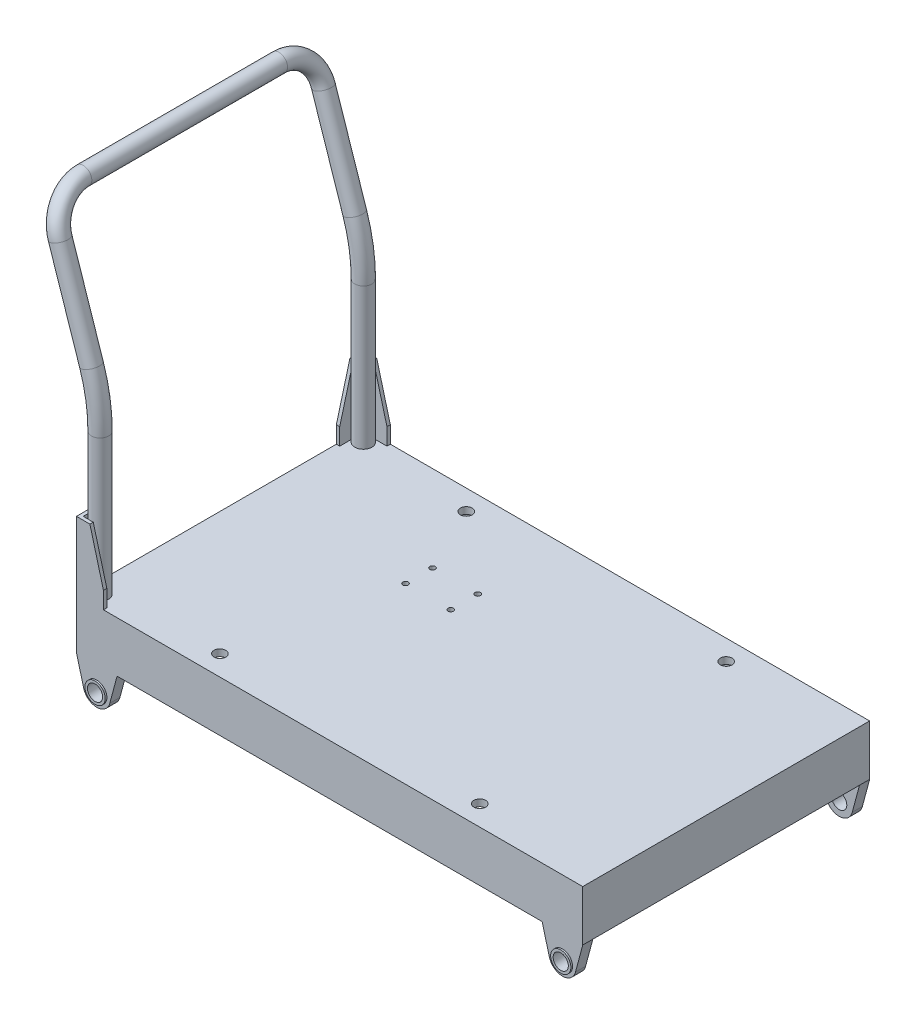
SolidWorks part; units mm, degrees
note: The reader was unsure of these and kept them because the rebuilt part matched: shared geometry of "草圖1<2>".
ref_plane "前基準面" through (0, 0, 0) normal (0, 0, 1) x (1, 0, 0)
ref_plane "上基準面" through (0, 0, 0) normal (0, 1, 0) x (1, 0, 0)
ref_plane "右基準面" through (0, 0, 0) normal (1, 0, 0) x (0, 0, -1)
sketch "草圖1" plane through (0, 0, 0) normal (0, 1, 0) x (1, 0, 0)
  line L1 (-75, -42.5) -> (75, -42.5)
  line L2 (-75, -42.5) -> (-75, 42.5)
  line L3 (-75, 42.5) -> (75, 42.5)
  line L4 (75, -42.5) -> (75, 42.5)
  line L5 (-75, -42.5) -> (75, 42.5) construction
  line L6 (-75, 42.5) -> (75, -42.5) construction
  point P0 (0, 0)
  dimension "D1" = 85
  dimension "D2" = 150
extrude "填料-伸長1" add sketch "草圖1" against normal blind 2
extrude "伸長-薄件1" add sketch "草圖1<2>" against normal blind 15 thin thin type one direction reverse wall 3
sketch "草圖1<2>" plane through (0, 0, 0) normal (0, 1, 0) x (1, 0, 0) same geometry as "草圖1"
sketch "草圖3" plane through (0, 0, 42.5) normal (0, 0, 1) x (1, 0, 0)
  line L0 (-75, 0) -> (75, 0) construction
  line L1 (-5, -12.5) -> (5, -12.5)
  line L2 (-5, -12.5) -> (-5, -2.5)
  line L3 (-5, -2.5) -> (5, -2.5)
  line L4 (5, -12.5) -> (5, -2.5)
  line L5 (-5, -12.5) -> (5, -2.5) construction
  line L6 (-5, -2.5) -> (5, -12.5) construction
  point P0 (0, -7.5)
  dimension "D1" = 10
  dimension "D2" = 7.5
sketch "草圖4" plane through (0, 0, 42.5) normal (0, 0, 1) x (1, 0, 0)
  line L2 (-75, -15) -> (-72.847, -23.0353)
  line L4 (0, 0) -> (0, 11.7436) construction
  line L5 (62.9665, -15) -> (75, -15)
  line L6 (65.1195, -23.0353) -> (62.9665, -15)
  line L7 (75, -15) -> (72.847, -23.0353)
  line L8 (-65.1195, -23.0353) -> (-62.9665, -15)
  line L9 (-62.9665, -15) -> (-75, -15)
  arc A1 (72.847, -23.0353) -> (65.1195, -23.0353) centre (68.9833, -22) cw
  circle A3 centre (68.9833, -22) radius 2.25
  circle A4 centre (-68.9833, -22) radius 2.25
  arc A5 (-72.847, -23.0353) -> (-65.1195, -23.0353) centre (-68.9833, -22) ccw
extrude "填料-伸長2" add sketch "草圖4" against normal blind 3
mirror "鏡射1" about plane through (0, 0, 0) normal (0, 0, 1) of "填料-伸長2"
sketch "草圖6" plane through (0, 0, 0) normal (0, 1, 0) x (1, 0, 0)
  line L0 (-69.8038, 0) -> (0, 0) construction
  line L1 (0, 0) -> (0, -59.3094) construction
  circle A0 centre (-38.5, -36.5) radius 1.75
  circle A1 centre (38.5, -36.5) radius 1.75
  circle A2 centre (38.5, 36.5) radius 1.75
  circle A3 centre (-38.5, 36.5) radius 1.75
  dimension "D1" = 73
  dimension "D2" = 77
  dimension "D3" = 3.5
extrude "除料-伸長2" cut sketch "草圖6" against normal up to next
sketch "草圖7" plane through (0, 0, 0) normal (0, 1, 0) x (1, 0, 0)
  line L0 (0, 0) -> (-65, 0) construction
  line L1 (-65, 0) -> (-65, -35) construction
  line L2 (-69, -35) -> (-61, -35) construction
  circle A0 centre (-69, -35) radius 1
  circle A1 centre (-61, -35) radius 1
  dimension "D4" = 2
  dimension "D1" = 8
  dimension "D2" = 65
  dimension "D3" = 35
sketch "草圖10" plane through (0, 0, 0) normal (0, 1, 0) x (1, 0, 0)
  line L0 (-75, 42.5) -> (-75, -42.5) construction
  line L1 (-75, 42.5) -> (-75, -42.5)
  line L2 (-75, -42.5) -> (75, -42.5) construction
  line L3 (-75, -42.5) -> (75, -42.5)
  line L5 (-75, -42.5) -> (-74, -42.5)
  line L6 (-75, -42.5) -> (-75, -34.5)
  line L7 (-75, -34.5) -> (-74, -34.5)
  line L8 (-74, -42.5) -> (-74, -34.5)
  line L9 (-75, -42.5) -> (-67, -42.5)
  line L10 (-75, -42.5) -> (-75, -41.5)
  line L11 (-75, -41.5) -> (-67, -41.5)
  line L12 (-67, -42.5) -> (-67, -41.5)
  circle A0 centre (-71.5, -39) radius 2.5 construction
  dimension "D2" = 5
  dimension "D1" = 1
  dimension "D3" = 8
extrude "填料-伸長4" add sketch "草圖10" along normal blind 20 contours L10 L11 L12 L9 | L5 L8 L7 L6
chamfer "導角1" distance 15 angle 15 2 edges at (-74.5, 20, 34.5) (-67, 20, 42)
sketch "草圖13" plane through (0, 0, 42.5) normal (0, 0, 1) x (1, 0, 0)
  line L0 (0, 0) -> (0, 11.7436) construction
  line L1 (0, 0) -> (0, 11.7436) construction
  circle A0 centre (68.9833, -22) radius 3
  circle A1 centre (68.9833, -22) radius 2.25 construction
  circle A2 centre (68.9833, -22) radius 2.25
  circle A3 centre (-68.9833, -22) radius 2.25
  circle A4 centre (-68.9833, -22) radius 3
  dimension "D1" = 6
extrude "填料-伸長5" add sketch "草圖13" along normal blind 0.5
mirror "鏡射2" about plane through (0, 0, 0) normal (0, 0, 1) of "填料-伸長5", "導角1", "填料-伸長4"
sketch3d "3D草圖1"
  line L0 (-71.5, 0, 39) -> (-71.5, 41.8861, 39)
  line L1 (-71.5, 50, 39) -> (-86.5, 50, 39) construction
  line L2 (-86.5, 50, 39) -> (-86.5, 95, 39) construction
  line L3 (-83.3377, 85.5132, 39) -> (-74.0658, 57.6975, 39)
  line L4 (-86.5, 95, 29) -> (-86.5, 95, -29)
  line L7 (-86.5, 95, -39) -> (-86.5, 50, -39) construction
  line L9 (-86.5, 50, -39) -> (-71.5, 50, -39) construction
  line L10 (-83.3377, 85.5132, -39) -> (-74.0658, 57.6975, -39)
  line L11 (-71.5, 41.8861, -39) -> (-71.5, 0, -39)
  arc A1 (-86.5, 95, -29) -> (-83.3377, 85.5132, -39) centre (-83.3377, 85.5132, -29) ccw
  arc A2 (-86.5, 95, 29) -> (-83.3377, 85.5132, 39) centre (-83.3377, 85.5132, 29) ccw
  arc A3 (-71.5, 41.8861, 39) -> (-74.0658, 57.6975, 39) centre (-121.5, 41.8861, 39) ccw
  arc A4 (-71.5, 41.8861, -39) -> (-74.0658, 57.6975, -39) centre (-121.5, 41.8861, -39) ccw
  point P18 (-86.5, 95, -39)
  point P20 (-92.8246, 82.3509, -29)
  point P23 (-86.5, 95, 39)
  point P25 (-73.8509, 88.6754, 29)
  point P28 (-71.5, 50, 39)
  point P30 (-121.5, 41.8861, 89)
  point P33 (-71.5, 50, -39)
  point P35 (-121.5, 41.8861, 11)
  dimension "D6" = 10
  dimension "D7" = 50
  dimension "D1" = 50
  dimension "D2" = 15
  dimension "D3" = 45
  dimension "D5" = 78
sketch "草圖12" plane through (0, 0, 0) normal (0, 1, 0) x (1, 0, 0)
  circle A2 centre (-71.5, 39) radius 2.55
  dimension "D1" = 5.1
sweep "掃出17" add profiles "草圖12" path "3D草圖1"
hole_wizard "M2 螺紋孔1" positions "草圖14" profile "草圖15" tap size "M2" standard "ISO" end condition up to next
sketch "草圖14" plane through (0, 0, 0) normal (0, 1, 0) x (1, 0, 0)
  line L0 (-75, 34.5) -> (-75, -34.5) construction
  line L1 (75, 42.5) -> (-67, 42.5) construction
  point P0 (-29, 17)
  point P2 (-15.6, 17)
  point P4 (-15.6, 9)
  point P6 (-29, 9)
  dimension "D1" = 8
  dimension "D2" = 13.4
  dimension "D3" = 46
  dimension "D4" = 25.5
sketch "草圖15" plane through (-29, 0, -17) normal (1, 0, 0) x (0, 0, 1)
  line L0 (0, 0) -> (0, 2)
  line L1 (0, 2) -> (0.8, 2)
  line L2 (0.8, 2) -> (0.8, 0)
  line L5 (0.8, 0) -> (0, 0)
  line L11 (0, -6.35) -> (0, 107.95) construction
  dimension "貫穿螺孔鑽直徑" = 1.6
  dimension "貫穿螺孔鑽深度" = 2
cosmetic thread "鑽孔螺紋1" parameters "D2"=2
cosmetic thread "鑽孔螺紋2" parameters "D2"=2
cosmetic thread "鑽孔螺紋3" parameters "D2"=2
cosmetic thread "鑽孔螺紋4" parameters "D2"=2
